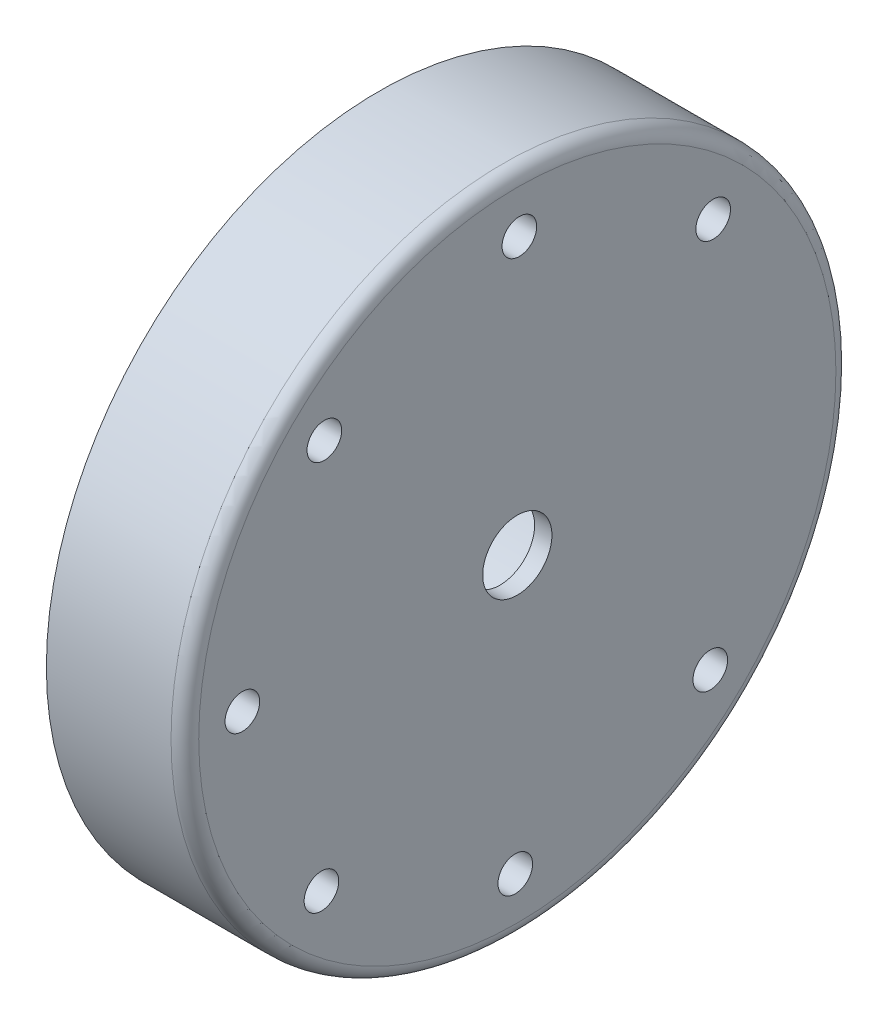
SolidWorks part; units mm, degrees
material "6061 Alloy"
ref_plane "Front Plane" through (0, 0, 0) normal (0, 0, 1) x (1, 0, 0)
ref_plane "Top Plane" through (0, 0, 0) normal (0, 1, 0) x (1, 0, 0)
ref_plane "Right Plane" through (0, 0, 0) normal (1, 0, 0) x (0, 0, -1)
sketch "Sketch1" plane through (0, 0, 0) normal (1, 0, 0) x (0, 0, -1)
  circle A0 centre (0, 0) radius 60.96
extrude "Boss-Extrude1" add sketch "Sketch1" along normal blind 25.4
fillet "Fillet1" radius 2.54 1 edges at (25.4, 0, -60.96)
sketch "Sketch2" plane through (25.4, 0, 0) normal (1, 0, 0) x (0, 0, -1)
  circle A0 centre (0, 0) radius 4.508
extrude "Cut-Extrude1" cut sketch "Sketch2" against normal blind 6.35
sketch "Sketch3" plane through (25.4, 0, 0) normal (1, 0, 0) x (0, 0, -1)
  circle A0 centre (22.5439, 0) radius 3.175
extrude "Cut-Extrude2" [suppressed] cut sketch "Sketch3" against normal blind 19.05
pattern_circular "CirPattern1" [suppressed] count 8 over 360 of bodies 103
sketch "Sketch4" plane through (25.4, 0, 0) normal (1, 0, 0) x (0, 0, -1)
  circle A0 centre (0, 0) radius 25.019
extrude "Cut-Extrude3" cut sketch "Sketch4" against normal through all
sketch "Sketch5" plane through (0, 0, 0) normal (-1, 0, 0) x (0, 0, 1)
  circle A0 centre (-35.9173, 35.3839) radius 3.175
extrude "Cut-Extrude4" cut sketch "Sketch5" against normal through all contours A0
pattern_circular "CirPattern2" count 8 over 360 about axis through (25.4, 0, 0) along (1, 0, 0) skipping 7 of "Cut-Extrude4"
sketch "Sketch6" plane through (25.4, 0, 0) normal (1, 0, 0) x (0, 0, -1)
  circle A0 centre (0, 0) radius 25.019
  circle A1 centre (0, 0) radius 6.35
extrude "Boss-Extrude2" add sketch "Sketch6" against normal blind 6.35
sketch "Sketch7" plane through (19.05, 0, 0) normal (-1, 0, 0) x (0, 0, 1)
  circle A0 centre (0, 0) radius 21.844
extrude "Cut-Extrude5" cut sketch "Sketch7" against normal blind 3.175
